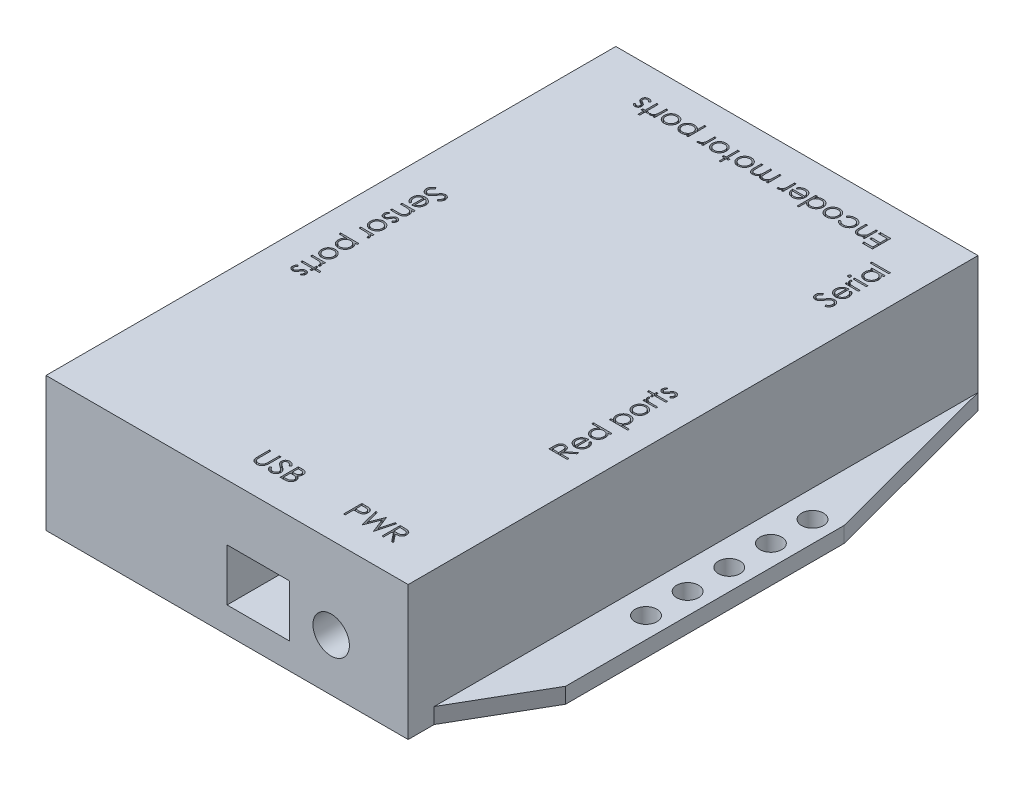
SolidWorks part; units mm, degrees
ref_plane "Front Plane" through (0, 0, 0) normal (0, 0, 1) x (1, 0, 0)
ref_plane "Top Plane" through (0, 0, 0) normal (0, 1, 0) x (1, 0, 0)
ref_plane "Right Plane" through (0, 0, 0) normal (1, 0, 0) x (0, 0, -1)
sketch "Sketch1" plane through (0, 0, 0) normal (0, 1, 0) x (1, 0, 0)
  line L1 (-34.8, 0) -> (34.8, 0)
  line L2 (-34.8, 0) -> (-34.8, 109.5)
  line L3 (-34.8, 109.5) -> (34.8, 109.5)
  line L4 (34.8, 0) -> (34.8, 109.5)
  point P6 (0, 0)
  dimension "D1" = 69.6
  dimension "D2" = 109.5
extrude "Boss-Extrude1" add sketch "Sketch1" along normal blind 25.8
sketch "Sketch2" plane through (0, 0, 0) normal (0, 1, 0) x (1, 0, 0)
  line L0 (-34.8, 109.5) -> (-44.05, 74.5)
  line L1 (-34.8, 109.5) -> (-34.8, 0) construction
  line L2 (-44.05, 74.5) -> (-44.05, 21)
  line L3 (-44.05, 21) -> (-34.8, 5)
  line L4 (-34.8, 5) -> (-34.8, 109.5)
  dimension "D3" = 16
  dimension "D1" = 35
  dimension "D4" = 5
  dimension "D2" = 44.05
extrude "Boss-Extrude2" add sketch "Sketch2" along normal blind 3
sketch "Sketch3" plane through (0, 3, 0) normal (0, 1, 0) x (1, 0, 0)
  line L0 (0, -1000) -> (0, 49000) construction
  line L1 (-40, 13.9946) -> (-40, 89.8243) construction
  line L2 (-34.8, 109.5) -> (-44.05, 74.5) construction
  line L3 (-44.05, 21) -> (-34.8, 5) construction
  line L4 (34.8, 109.5) -> (-34.8, 109.5) construction
  line L5 (-34.8, 0) -> (34.8, 0) construction
  circle A5 centre (-40, 72.5) radius 2.1
  circle A6 centre (-40, 64.5) radius 2.1
  circle A7 centre (-40, 56.5) radius 2.1
  circle A8 centre (-40, 48.5) radius 2.1
  circle A9 centre (-40, 40.5) radius 2.1
  dimension "D1" = 4.2
  dimension "D2" = 16
  dimension "D3" = 16
  dimension "D4" = 8
  dimension "D5" = 8
  dimension "D8" = 40
  dimension "D6" = 39.1
  dimension "D7" = 42.6
extrude "Cut-Extrude1" cut sketch "Sketch3" against normal through all
mirror "Mirror1" about plane through (0, 0, 0) normal (1, 0, 0) of "Cut-Extrude1", "Boss-Extrude2"
sketch "Sketch4" plane through (0, 0, 0) normal (0, 0, 1) x (1, 0, 0)
  line L0 (-34.8, 0) -> (34.8, 0) construction
  line L1 (0, 15) -> (12, 15)
  line L2 (0, 15) -> (0, 5)
  line L3 (0, 5) -> (12, 5)
  line L4 (12, 15) -> (12, 5)
  circle A0 centre (20, 10) radius 3.5
  point P14 (12, 10)
  dimension "D3" = 7
  dimension "D5" = 8
  dimension "D1" = 12
  dimension "D2" = 10
  dimension "D4" = 5
extrude "Cut-Extrude2" cut sketch "Sketch4" against normal blind 10
sketch "Sketch5" plane through (0, 25.8, 0) normal (0, 1, 0) x (1, 0, 0)
  line L0 (-34.8, 103.95) -> (34.8, 103.95) construction
  line L1 (-34.8, 109.5) -> (-34.8, 0) construction
  line L2 (34.8, 0) -> (34.8, 109.5) construction
  line L3 (34.8, 109.5) -> (-34.8, 109.5) construction
  line L4 (-34.8, 5.55) -> (34.8, 5.55) construction
  line L5 (-34.8, 0) -> (34.8, 0) construction
  line L6 (-29.25, 5.55) -> (-29.25, 103.95) construction
  line L7 (29.25, 103.95) -> (29.25, 5.55) construction
  text T0 "Encoder motor ports"
  text T1 "USB       PWR      "
  text T2 "Sensor ports"
  text T3 "Red ports                     Serial    "
  dimension "D1" = 5.55
  dimension "D2" = 5.55
  dimension "D3" = 5.55
  dimension "D4" = 5.55
extrude "Cut-Extrude3" cut sketch "Sketch5" against normal blind 1
equation "\"width\"= 24"
equation "\"thk\"= 3"
equation "\"holesize\"= 4.2"
equation "\"holedistance\"= ( 20 + 12 ) / 2"
equation "\"threaded_hole\"= 3.9"
equation "\"fillet_radius\"= 2"
equation "\"ground_clearance\"= 25"
equation "\"tire_thk\"= 3"
equation "\"innerwheel_diam\" = \"wheel_diam\"-2*\"tire_thk\""
equation "\"innerwheel_thk\"= 8"
equation "\"wheel_diam\"= 2*(\"width\"/2+\"ground_clearance\")"
equation "\"D1@Sketch3\"=\"holesize\""
equation "\"D2@Sketch3\"=\"holedistance\""
equation "\"D3@Sketch3\"=\"holedistance\""
equation "\"D4@Sketch3\"=\"D2@Sketch3\"/2"
equation "\"D5@Sketch3\"=\"D3@Sketch3\"/2"
equation "\"D2@Sketch5\"=\"D1@Sketch5\""
equation "\"D3@Sketch5\"=\"D1@Sketch5\""
equation "\"D4@Sketch5\"=\"D2@Sketch5\""
equation "\"D8@Sketch3\"=80/2"
equation "\"D2@Sketch2\"=88.1/2"
equation "\"coloursensor_holesize\"= 2.65"
equation "\"hole_to_edge\" = 4"
